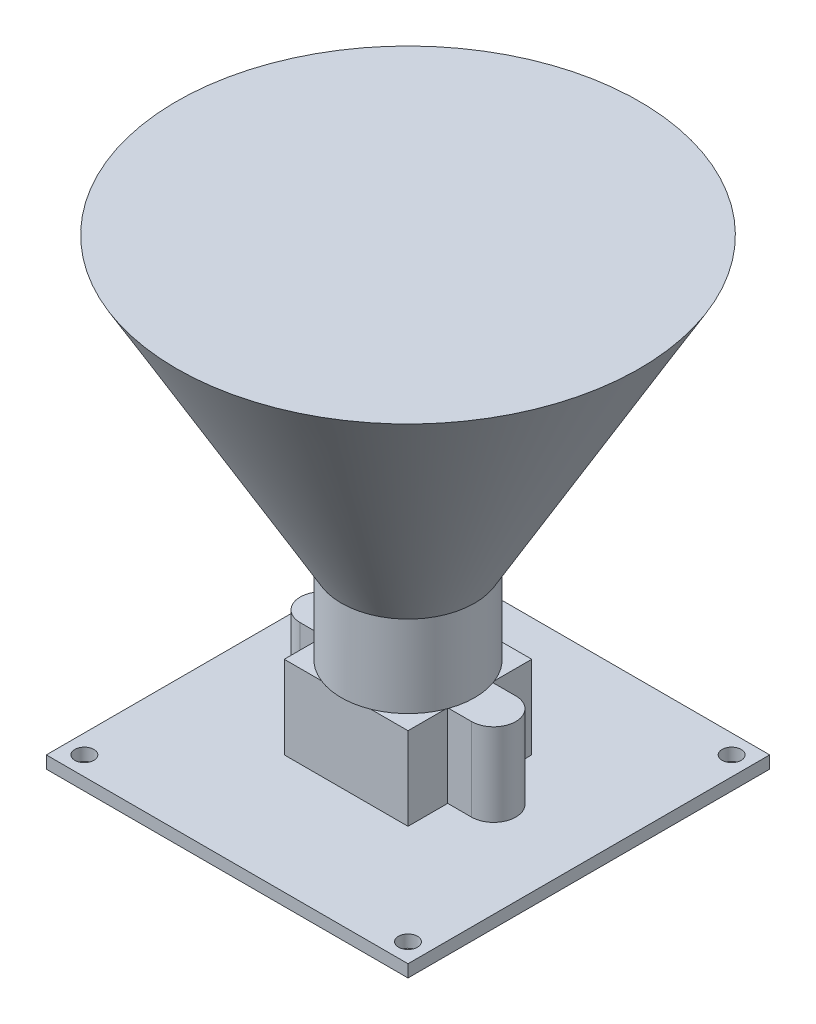
SolidWorks part; units mm, degrees
ref_plane "前视基准面" through (0, 0, 0) normal (0, 0, 1) x (1, 0, 0)
ref_plane "上视基准面" through (0, 0, 0) normal (0, 1, 0) x (1, 0, 0)
ref_plane "右视基准面" through (0, 0, 0) normal (1, 0, 0) x (0, 0, -1)
sketch "Sketch1" plane through (0, 0, 0) normal (0, 1, 0) x (1, 0, 0)
  line L0 (4.6135, 13.9942) -> (4.6135, 34.0904) construction
  line L5 (-14.3865, 13.9942) -> (23.6135, 13.9942)
  line L6 (-14.3865, 13.9942) -> (-14.3865, -24.0058)
  line L7 (-14.3865, -24.0058) -> (23.6135, -24.0058)
  line L8 (23.6135, 13.9942) -> (23.6135, -24.0058)
  line L9 (-14.3865, -5.0058) -> (-25.275, -5.0058) construction
  line L11 (-12.3865, -22.0058) -> (21.6135, -22.0058) construction
  line L12 (-12.3865, -22.0058) -> (-12.3865, 11.9942) construction
  line L13 (-12.3865, 11.9942) -> (21.6135, 11.9942) construction
  line L14 (21.6135, -22.0058) -> (21.6135, 11.9942) construction
  line L15 (-12.3865, -22.0058) -> (21.6135, 11.9942) construction
  line L16 (-12.3865, 11.9942) -> (21.6135, -22.0058) construction
  circle A0 centre (-12.3865, 11.9942) radius 1
  circle A1 centre (21.6135, 11.9942) radius 1
  circle A2 centre (21.6135, -22.0058) radius 1
  circle A3 centre (-12.3865, -22.0058) radius 1
  point P5 (4.6135, -5.0058)
  point P13 (4.6135, 13.9942)
  dimension "D1" = 38
  dimension "D2" = 38
  dimension "D3" = 34
  dimension "D4" = 34
extrude "Boss-Extrude1" add sketch "Sketch1" along normal blind 1.3
sketch "Sketch2" plane through (0, 1.3, 0) normal (0, 1, 0) x (1, 0, 0)
  line L0 (4.6135, 13.9942) -> (4.6135, -32.1036) construction
  line L2 (-14.3865, -5.0058) -> (-25.698, -5.0058) construction
  line L4 (-4.3865, -5.0058) -> (13.6135, -5.0058) construction
  line L5 (-1.8865, -11.5058) -> (11.1135, -11.5058)
  line L6 (-1.8865, -11.5058) -> (-1.8865, -7.3337)
  line L7 (-1.8865, 1.4942) -> (11.1135, 1.4942)
  line L8 (11.1135, -11.5058) -> (11.1135, -7.3337)
  line L9 (-1.8865, -11.5058) -> (11.1135, 1.4942) construction
  line L10 (-1.8865, 1.4942) -> (11.1135, -11.5058) construction
  line L11 (-4.3865, -2.6778) -> (-1.8865, -2.6778)
  line L12 (-4.3865, -7.3337) -> (-1.8865, -7.3337)
  line L13 (11.1135, -2.6778) -> (11.1135, 1.4942)
  line L14 (-1.8865, -2.6778) -> (-1.8865, 1.4942)
  line L15 (11.1135, -2.6778) -> (13.6135, -2.6778)
  line L16 (11.1135, -7.3337) -> (13.6135, -7.3337)
  arc A0 (-4.3865, -2.6778) -> (-4.3865, -7.3337) centre (-4.3865, -5.0058) ccw
  arc A1 (13.6135, -7.3337) -> (13.6135, -2.6778) centre (13.6135, -5.0058) ccw
  point P1 (4.6135, -5.0058)
  point P9 (4.6135, -5.0058)
  dimension "D1" = 13
  dimension "D2" = 13
  dimension "D3" = 18
extrude "Boss-Extrude2" add sketch "Sketch2" along normal blind 8.7
sketch "Sketch3" plane through (0, 10, 0) normal (0, 1, 0) x (1, 0, 0)
  circle A0 centre (4.6135, -5.0058) radius 7
extrude "Boss-Extrude3" add sketch "Sketch3" along normal blind 8.6
sketch "Sketch4" plane through (0, 18.6, 0) normal (0, 1, 0) x (1, 0, 0)
  circle A1 centre (4.6135, -5.0058) radius 7
  circle A2 centre (4.6135, -5.0058) radius 7
  dimension "D1" = 0
extrude "Boss-Extrude4" add sketch "Sketch4" along normal blind 30 draft 30 draft outward yes
ref_axis "基准轴1" through (4.6135, 18.6, 5.0058) along (0, -1, 0)
